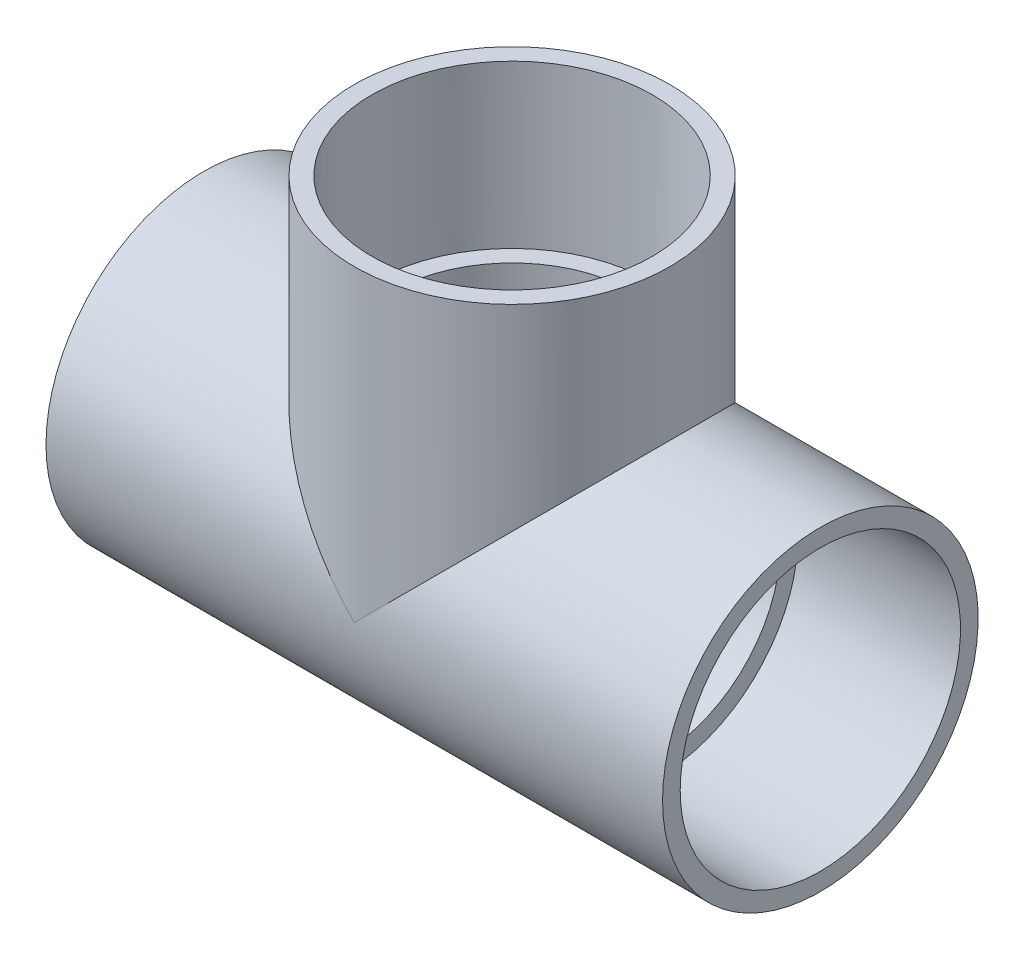
SolidWorks part; units mm, degrees
ref_plane "Front Plane" through (0, 0, 0) normal (0, 0, 1) x (1, 0, 0)
ref_plane "Top Plane" through (0, 0, 0) normal (0, 1, 0) x (1, 0, 0)
ref_plane "Right Plane" through (0, 0, 0) normal (1, 0, 0) x (0, 0, -1)
sketch "Sketch0" plane through (0, 0, 0) normal (0, 0, 1) x (1, 0, 0)
  line L0 (-66.675, 0) -> (0, 0) construction
  line L1 (0, 0) -> (0, 66.675) construction
  line L2 (-31.75, 0) -> (0, 0) construction
  line L3 (0, 0) -> (0, 31.75) construction
  line L4 (-66.675, 34.1313) -> (-66.675, -34.1313) construction
  line L5 (-31.75, 30.0863) -> (-66.675, 30.3149) construction
  line L6 (-31.75, 30.0863) -> (-31.75, -30.0863) construction
  line L7 (-31.75, -30.0863) -> (-66.675, -30.3149) construction
  line L8 (-66.675, 30.3149) -> (-66.675, -30.3149) construction
  line L9 (-34.1313, 66.675) -> (34.1313, 66.675) construction
  line L10 (-30.3149, 66.675) -> (30.3149, 66.675) construction
  line L11 (30.3149, 66.675) -> (30.0863, 31.75) construction
  line L12 (30.0863, 31.75) -> (-30.0863, 31.75) construction
  line L13 (-30.0863, 31.75) -> (-30.3149, 66.675) construction
  line L14 (-31.75, 26.2509) -> (-31.75, -26.2509) construction
  line L18 (-26.2509, 31.75) -> (26.2509, 31.75) construction
  dimension "H" = 66.675
  dimension "G" = 31.75
  dimension "M" = 68.2625
  dimension "OD A" = 60.6298
  dimension "OD B" = 60.1726
  dimension "ID" = 52.5018
sketch "Sketch1" plane through (0, 0, 0) normal (0, 0, 1) x (1, 0, 0)
  line L0 (-66.675, 0) -> (0, 0) construction
  line L1 (-66.675, 0) -> (0, 0) construction
  line L3 (-66.675, -34.1313) -> (-31.75, -34.1313)
  line L4 (-66.675, -34.1313) -> (-66.675, -30.3149)
  line L5 (-66.675, -30.3149) -> (-31.75, -30.0863)
  line L6 (-31.75, -34.1313) -> (-31.75, -30.0863)
revolve "Revolve1" add sketch "Sketch1" angle 360 about L1
mirror "Mirror1" about plane through (0, 0, 0) normal (1, 0, 0) of bodies 102
sketch "Sketch2" plane through (0, 0, 0) normal (0, 0, 1) x (1, 0, 0)
  line L0 (30.3149, 66.675) -> (30.0863, 31.75)
  line L1 (30.0863, 31.75) -> (34.1313, 31.75)
  line L2 (34.1313, 31.75) -> (34.1313, 66.675)
  line L3 (34.1313, 66.675) -> (30.3149, 66.675)
  line L4 (0, 0) -> (0, 66.675) construction
  line L5 (0, 0) -> (0, 66.675) construction
revolve "Revolve2" add sketch "Sketch2" angle 360 about L5
sketch "Sketch3" plane through (-31.75, 0, 0) normal (1, 0, 0) x (0, 0, -1)
  line L0 (-34.1313, 31.75) -> (34.1313, 31.75) construction
  line L2 (12.5252, 31.75) -> (-12.5252, 31.75)
  circle A1 centre (0, 0) radius 34.1313 construction
  arc A3 (-12.5252, 31.75) -> (12.5252, 31.75) centre (0, 0) ccw
extrude "Boss-Extrude1" add sketch "Sketch3" along normal up to surface (63.5 mm away) up to face at (31.75, 0, 30.0863)
sketch "Sketch4" plane through (0, 31.75, 0) normal (0, -1, 0) x (1, 0, 0)
  line L0 (31.75, -12.5252) -> (31.75, 12.5252)
  line L1 (-31.75, -12.5252) -> (-31.75, 12.5252)
  circle A0 centre (0, 0) radius 34.1313 construction
  arc A1 (31.75, 12.5252) -> (-31.75, 12.5252) centre (0, 0) ccw
  arc A2 (-31.75, -12.5252) -> (31.75, -12.5252) centre (0, 0) ccw
  circle A3 centre (0, 0) radius 34.1313 construction
  circle A4 centre (0, 0) radius 34.1313 construction
extrude "Boss-Extrude2" add sketch "Sketch4" along normal up to surface (31.75 mm away) up to plane "Top Plane"
sketch "Sketch5" plane through (-31.75, 0, 0) normal (-1, 0, 0) x (0, 0, 1)
  line L0 (0, 30.0863) -> (0, -30.0863) construction
  circle A0 centre (0, 0) radius 26.2509
extrude "Cut-Extrude1" cut sketch "Sketch5" against normal up to surface (63.5 mm away) up to face at (31.75, 0, 30.0863)
sketch "Sketch6" plane through (0, 31.75, 0) normal (0, 1, 0) x (1, 0, 0)
  circle A0 centre (0, 0) radius 26.2509
extrude "Cut-Extrude2" cut sketch "Sketch6" against normal up to vertex (31.75 mm away) up to point (0, 0, 0)
other "CPoint1" parameters "Diameter"=50.8, "StubLength"=152.4
ref_axis "Axis1" through (0, 41.75, 0) along (0, -1, 0)
other "CPoint2" parameters "Diameter"=50.8, "StubLength"=152.4
ref_axis "Axis2" through (-41.75, 0, 0) along (1, 0, 0)
other "CPoint3" parameters "Diameter"=50.8, "StubLength"=152.4
ref_axis "Axis3" through (41.75, 0, 0) along (-1, 0, 0)
other "RPoint1"
